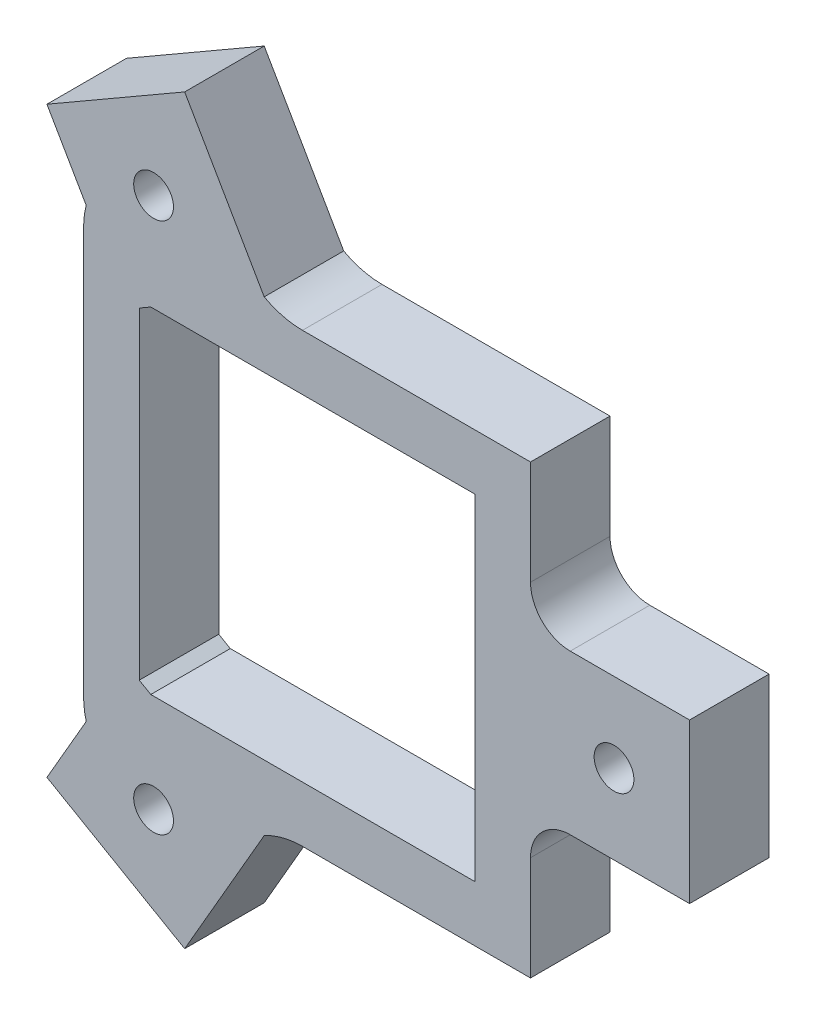
SolidWorks part; units mm, degrees
note: '?' marks a value the reader was unsure of.
ref_plane "Ebene vorne" through (0, 0, 0) normal (0, 0, 1) x (1, 0, 0)
ref_plane "Ebene oben" through (0, 0, 0) normal (0, 1, 0) x (1, 0, 0)
ref_plane "Ebene rechts" through (0, 0, 0) normal (1, 0, 0) x (0, 0, -1)
sketch "Skizze2" plane through (0, 0, 0) normal (0, 0, 1) x (1, 0, 0)
  line L1 (0, 0) -> (42.2, 0)
  line L2 (0, 0) -> (0, 42.2)
  line L3 (0, 42.2) -> (42.2, 42.2)
  line L4 (42.2, 0) -> (42.2, 42.2)
  line L5 (-7, 49.2) -> (49.2, 49.2)
  line L6 (-7, 49.2) -> (-7, -7)
  line L7 (-7, -7) -> (49.2, -7)
  line L8 (49.2, 49.2) -> (49.2, -7)
  dimension "D1" = 42.2
  dimension "D2" = 42.2
  dimension "D3" = 7
  dimension "D4" = 7
  dimension "D5" = 7
  dimension "D6" = 7
extrude "Aufsatz-Linear austragen1" add sketch "Skizze2" along normal blind 10
ref_plane "Ebene1" through (0, 0, 0) normal (0, 0, -1) x (-1, 0, 0)
sketch "Skizze5" plane through (0, 0, 0) normal (0, 0, -1) x (-1, 0, 0)
  line L5 (0, 42.2) -> (0, 0) construction
  line L6 (0, 0) -> (-42.2, 0) construction
  circle A0 centre (-21.1, 21.1) radius 13.1788
  dimension "D1" = 21.1
  dimension "D2" = 21.1
ref_axis "Achse1" through (21.1, 21.1, 0) along (0, 0, -1)?
sketch "Skizze3" plane through (49.2, 0, 0) normal (1, 0, 0) x (0, 0, -1)
  line L0 (-10, -7) -> (-10, 49.2) construction
  line L1 (-10, 31.1) -> (0, 31.1)
  line L2 (-10, 31.1) -> (-10, 11.1)
  line L3 (-10, 11.1) -> (0, 11.1)
  line L4 (0, 31.1) -> (0, 11.1)
  line L5 (0, -7) -> (0, 49.2) construction
  line L6 (-10, -7) -> (0, -7) construction
  dimension "D1" = 20
  dimension "D2" = 18.1
extrude "Aufsatz-Linear austragen2" add sketch "Skizze3" along normal blind 20
sketch "Skizze4" plane through (0, 0, 10) normal (0, 0, 1) x (1, 0, 0)
  line L0 (42.2, 0) -> (42.2, 42.2) construction
  circle A0 centre (59.7, 21.1) radius 2.5
  dimension "D2" = 5
  dimension "D1" = 17.5
extrude "Schnitt-Linear austragen1" cut sketch "Skizze4" against normal blind 27 contours A0
pattern_circular "Kreismuster1" count 3 over 360 about axis through (21.1, 21.1, 0) along (0, 0, 1) of "Aufsatz-Linear austragen2"
pattern_circular "Kreismuster2" count 3 over 360 about axis through (21.1, 21.1, 0) along (0, 0, 1) of "Schnitt-Linear austragen1"
fillet "Verrundung1" radius 10 1 edges at (13.5706, 49.2, 5)
fillet "Verrundung2" radius 10 1 edges at (-7, 49.2, 5)
fillet "Verrundung3" radius 10 2 edges at (13.5706, -7, 5) (-7, -7, 5)
fillet "Verrundung4" radius 5 2 edges at (49.2, 31.1, 5) (49.2, 11.1, 5)
